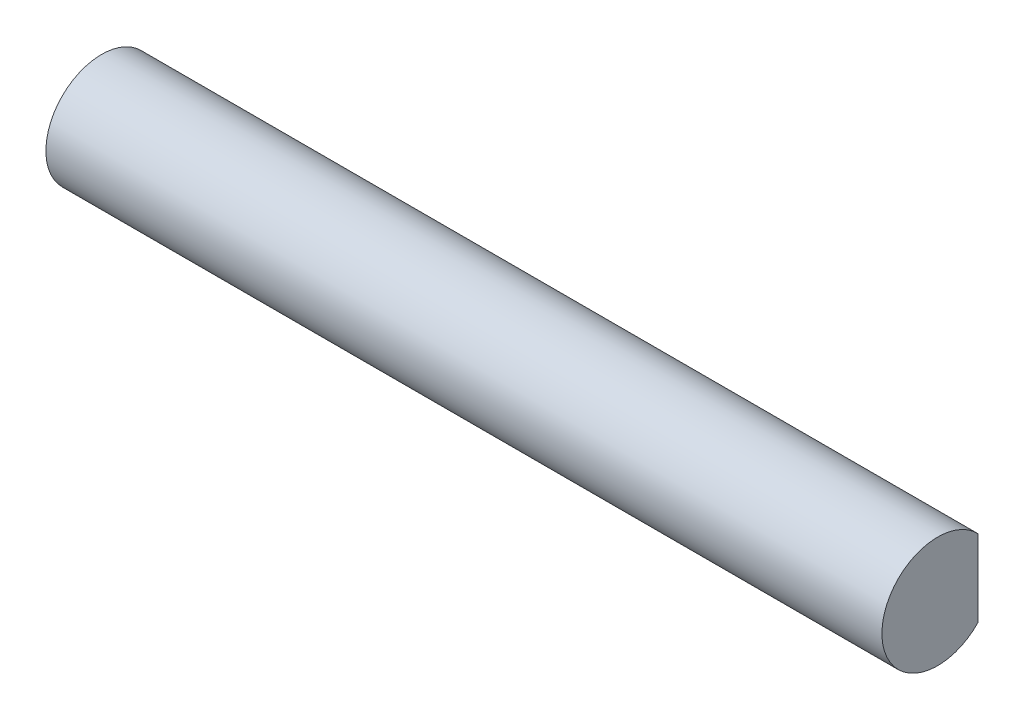
SolidWorks part; units mm, degrees
ref_plane "Front Plane" through (0, 0, 0) normal (0, 0, 1) x (1, 0, 0)
ref_plane "Top Plane" through (0, 0, 0) normal (0, 1, 0) x (1, 0, 0)
ref_plane "Right Plane" through (0, 0, 0) normal (1, 0, 0) x (0, 0, -1)
sketch "Sketch5" plane through (0, 0, 3.7) normal (1, 0, 0) x (0, 1, 0)
  line L0 (0, -14.7) -> (0, 7.3) construction
  line L5 (-7.5, -2.6947) -> (-6.4, -4.6) construction
  line L6 (7.5, -2.6947) -> (6.4, -4.6) construction
  line L7 (5.3668, 1) -> (7.5, -2.6947) construction
  line L8 (-5.3668, 1) -> (5.3668, 1) construction
  line L9 (-5.3668, 1) -> (-7.5, -2.6947) construction
  line L10 (7.7309, -2.6947) -> (6.5732, -4.7)
  line L11 (5.4823, 1.2) -> (7.7309, -2.6947)
  line L12 (-5.4823, 1.2) -> (5.4823, 1.2)
  line L13 (-5.4823, 1.2) -> (-7.7309, -2.6947)
  line L14 (-7.7309, -2.6947) -> (-6.5732, -4.7)
  line L15 (-6.5732, -4.7) -> (6.5732, -4.7)
  line L17 (0, -9.7207) -> (0, 9.7207) construction
  line L18 (-6.9, -10.9381) -> (6.9, -10.9381)
  line L19 (0, -10.9381) -> (0, -3.7) construction
  circle A0 centre (0, -3.7) radius 10 construction
  arc A1 (-6.9, -10.9381) -> (6.9, -10.9381) centre (0, -3.7) cw
  point P18 (0, -13.7)
sketch "Sketch8" plane through (0, 0, 3.7) normal (0, -1, 0) x (1, 0, 0)
  line L2 (0, -9.7207) -> (-145, -9.7207)
  line L3 (0, -9.9381) -> (-145, -9.9381)
  line L4 (0, -10.9381) -> (-150, -10.9381)
  point P0 (0, -9.7207)
  point P1 (0.0193, -10.0619)
  point P3 (0, -10.9381)
  point P4 (0, -10.1696)
  point P5 (0, 0)
  point P6 (0, -10.079)
  point P15 (-145, -9.9886)
  point P16 (0, -10.2652)
  point P19 (0, -10)
sketch "Sketch9" plane through (0, 0, 3.7) normal (1, 0, 0) x (0, 1, 0)
  line L0 (-6.9, -10.9381) -> (6.9, -10.9381) construction
  line L3 (-6.9, -10.9381) -> (6.9, -10.9381) construction
  line L4 (-6.4874, -9.9381) -> (6.4874, -9.9381)
  line L5 (-6.4017, -9.7381) -> (6.4017, -9.7381)
  arc A3 (6.9, -10.9381) -> (-6.9, -10.9381) centre (0, -3.7) ccw construction
  arc A4 (6.4874, -9.9381) -> (-6.4874, -9.9381) centre (0, -3.7) ccw
  arc A5 (6.4017, -9.7381) -> (-6.4017, -9.7381) centre (0, -3.7) ccw
sketch "Sketch1" plane through (0, 0, 0) normal (1, 0, 0) x (0, 0, -1)
  line L37 (7.2381, -6.9) -> (7.2381, 6.9) construction
  line L39 (7.2381, -6.9) -> (7.2381, 6.9)
  line L42 (1, 6.5732) -> (-1.0053, 7.7309)
  line L43 (1, -6.5732) -> (1, 6.5732)
  line L44 (-1.0053, -7.7309) -> (1, -6.5732)
  line L45 (-4.9, -5.4823) -> (-1.0053, -7.7309)
  line L46 (-4.9, 5.4823) -> (-4.9, -5.4823)
  line L47 (-1.0053, 7.7309) -> (-4.9, 5.4823)
  line L48 (1, 6.5732) -> (-1.0053, 7.7309)
  line L49 (1, -6.5732) -> (1, 6.5732)
  line L50 (-1.0053, -7.7309) -> (1, -6.5732)
  line L51 (-4.9, -5.4823) -> (-1.0053, -7.7309)
  line L52 (-4.9, 5.4823) -> (-4.9, -5.4823)
  line L53 (-1.0053, 7.7309) -> (-4.9, 5.4823)
  arc A5 (7.2381, 6.9) -> (7.2381, -6.9) centre (0, 0) ccw construction
  arc A6 (7.2381, 6.9) -> (7.2381, -6.9) centre (0, 0) ccw
  dimension "D2" = 0
extrude "Bar" add sketch "Sketch1" against normal up to vertex (150 mm away) up to point (-150, 0, -7.2381)
sketch "Sketch10" plane through (-150, 0, 0) normal (-1, 0, 0) x (0, 0, 1)
  line L0 (-6.2381, -6.4874) -> (-6.2381, 6.4874) construction
  line L1 (-6.2381, -6.4874) -> (-6.2381, 6.4874)
  arc A0 (-6.2381, -6.4874) -> (-6.2381, 6.4874) centre (0, 0) ccw construction
  arc A1 (-6.2381, -6.4874) -> (-6.2381, 6.4874) centre (0, 0) ccw
extrude "Cut-Extrude4" cut sketch "Sketch10" against normal up to vertex (5 mm away) up to point (-145, 0, -6.2381)
sketch "Sketch6" plane through (0, 0, -7.2381) normal (0, 0, -1) x (1, 0, 0)
  line L12 (0, 0) -> (-150, 0) construction
  line L13 (-0.8, 6.1) -> (-49.7333, 6.1)
  line L14 (-0.8, 6.1) -> (-0.8, -6.1)
  line L15 (-0.8, -6.1) -> (-49.7333, -6.1)
  line L24 (0, -6.9) -> (0, 6.9)
  line L25 (0, 6.9) -> (-150, 6.9)
  line L26 (-150, 6.9) -> (-150, -6.9)
  line L27 (-150, -6.9) -> (0, -6.9)
  line L28 (0, -6.9) -> (0, 6.9) construction
  line L29 (0, 6.9) -> (-150, 6.9) construction
  line L30 (-150, 6.9) -> (-150, -6.9) construction
  line L31 (-150, -6.9) -> (0, -6.9) construction
  line L32 (-49.7333, 6.1) -> (-49.7333, -6.1)
  line L33 (-50.5333, 6.1) -> (-50.5333, -6.1)
  line L34 (-50.5333, 6.1) -> (-99.4667, 6.1)
  line L35 (-99.4667, 6.1) -> (-99.4667, -6.1)
  line L36 (-50.5333, -6.1) -> (-99.4667, -6.1)
  line L37 (-100.2667, 6.1) -> (-100.2667, -6.1)
  line L38 (-100.2667, 6.1) -> (-149.2, 6.1)
  line L39 (-149.2, 6.1) -> (-149.2, -6.1)
  line L40 (-100.2667, -6.1) -> (-149.2, -6.1)
  dimension "D2" = 0.8
  dimension "D3" = 0.8
  dimension "D5" = 0.8
  dimension "D6" = 0.8
  dimension "D1" = 0
  dimension "D4" = 3
extrude "Cut-Extrude3" cut sketch "Sketch6" against normal up to next
sketch "Sketch11" plane through (0, 0, 0) normal (1, 0, 0) x (0, 0, -1)
  line L1 (7.2381, -6.9) -> (7.2381, 6.9)
  line L2 (7.2381, -6.9) -> (7.2381, 6.9)
  arc A1 (7.2381, 6.9) -> (7.2381, -6.9) centre (0, 0) ccw
  arc A2 (7.2381, 6.9) -> (7.2381, -6.9) centre (0, 0) ccw
  dimension "D1" = 0
extrude "Boss-Extrude2" add sketch "Sketch11" against normal blind 0.8
